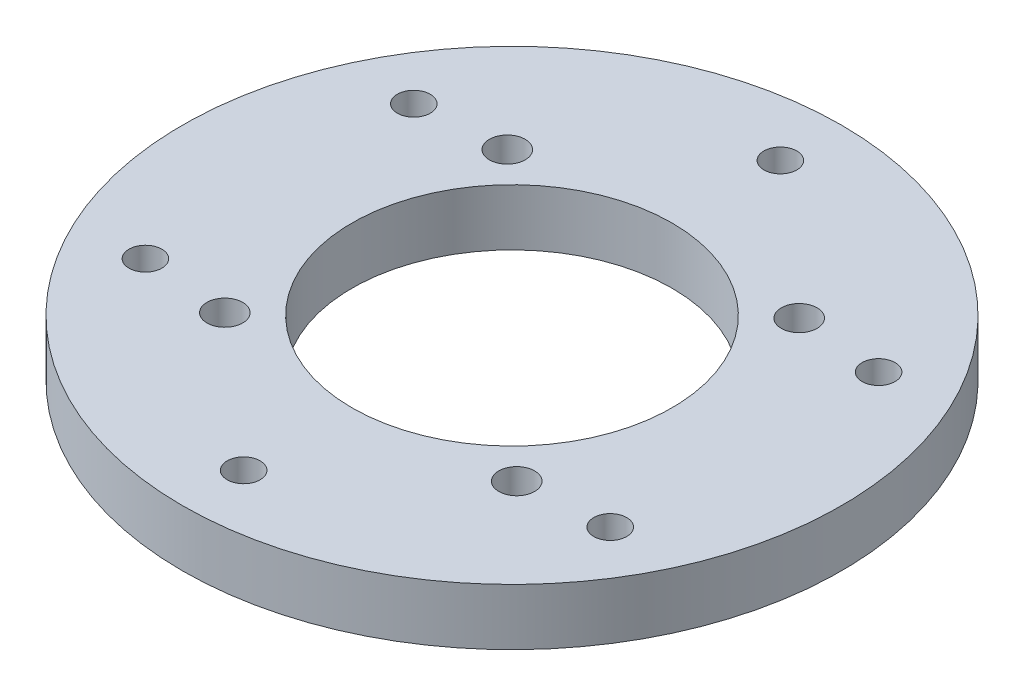
SolidWorks part; units mm, degrees
note: '?' marks a value the reader was unsure of.
material "2.0261 (CuZn28)"
ref_plane "前视基准面" through (0, 0, 0) normal (0, 0, 1) x (1, 0, 0)
ref_plane "上视基准面" through (0, 0, 0) normal (0, 1, 0) x (1, 0, 0)
ref_plane "右视基准面" through (0, 0, 0) normal (1, 0, 0) x (0, 0, -1)
sketch "草图1" plane through (0, 0, 0) normal (0, 1, 0) x (1, 0, 0)
  circle A0 centre (0, 0) radius 35
  dimension "D1" = 70
extrude "凸台-拉伸1" add sketch "草图1" along normal blind 6
sketch "草图2" plane through (0, 6, 0) normal (0, 1, 0) x (1, 0, 0)
  circle A0 centre (0, 0) radius 28.5
  dimension "D1" = 57
sketch "草图3" plane through (0, 6, 0) normal (0, 1, 0) x (1, 0, 0)
  circle A0 centre (0, 0) radius 28.5 construction
  point P0 (0, 28.5)
hole_wizard "孔1" positions "草图3" profile "草图4" legacy end condition up to next
sketch "草图4" plane through (0, 6, -28.5) normal (1, 0, 0) x (0, 0, 1)
  line L0 (0, 0) -> (0, 6)
  line L1 (0, 6) -> (1.75, 6)
  line L2 (1.75, 6) -> (1.75, 0)
  line L3 (1.75, 0) -> (0, 0)
  line L4 (0, 110) -> (0, -10) construction
  dimension "直径" = 3.5
  dimension "深度" = 6
ref_axis "基准轴1" through (0, 0, 0) along (0, 1, 0)?
pattern_circular "阵列(圆周)1" count 6 every 60 about axis through (0, 0, 0) along (0, 1, 0) of "孔1"
sketch "草图5" plane through (0, 6, 0) normal (0, 1, 0) x (1, 0, 0)
  line L1 (-15.5, 15) -> (15.5, 15)
  line L2 (-15.5, 15) -> (-15.5, -15)
  line L3 (-15.5, -15) -> (15.5, -15)
  line L4 (15.5, 15) -> (15.5, -15)
  line L5 (-15.5, 15) -> (15.5, -15) construction
  line L6 (-15.5, -15) -> (15.5, 15) construction
  point P0 (0, 0)
  dimension "D1" = 31
  dimension "D2" = 30
sketch "草图6" plane through (0, 6, 0) normal (0, 1, 0) x (1, 0, 0)
  point P0 (-15.5, 15)
  point P3 (15.5, 15)
  point P6 (15.5, -15)
  point P9 (-15.5, -15)
hole_wizard "孔2" positions "草图6" profile "草图7" legacy end condition up to next
sketch "草图7" plane through (-15.5, 6, -15) normal (1, 0, 0) x (0, 0, 1)
  line L0 (0, 0) -> (0, 6)
  line L1 (0, 6) -> (1.9, 6)
  line L2 (1.9, 6) -> (1.9, 0)
  line L3 (1.9, 0) -> (0, 0)
  line L4 (0, 110) -> (0, -10) construction
  dimension "直径" = 3.8
  dimension "深度" = 6
sketch "草图8" plane through (0, 6, 0) normal (0, 1, 0) x (1, 0, 0)
  circle A0 centre (0, 0) radius 11
  dimension "D1" = 22
extrude "切除-拉伸1" cut sketch "草图8" against normal blind 10
sketch "草图11" plane through (0, 0, 0) normal (0, -1, 0) x (-1, 0, 0)
  point P0 (-15.5, 15)
  point P3 (15.5, 15)
  point P6 (15.5, -15)
  point P9 (-15.5, -15)
hole_wizard "孔3" positions "草图11" profile "草图12" legacy
sketch "草图12" plane through (15.5, 0, -15) normal (1, 0, 0) x (0, 0, -1)
  line L0 (0, 0) -> (0, 1.5)
  line L1 (0, 1.5) -> (3.5, 1.5)
  line L2 (3.5, 1.5) -> (3.5, 0)
  line L3 (3.5, 0) -> (0, 0)
  line L4 (0, 110) -> (0, -10) construction
  dimension "直径" = 7
  dimension "深度" = 1.5
sketch "草图13" plane through (0, 0, 0) normal (0, -1, 0) x (1, 0, 0)
  line L0 (-15.5, 15) -> (15.5, -15) construction
  circle A0 centre (0, 0) radius 17
  dimension "D1" = 34
extrude "切除-拉伸2" cut sketch "草图13" against normal blind 10
